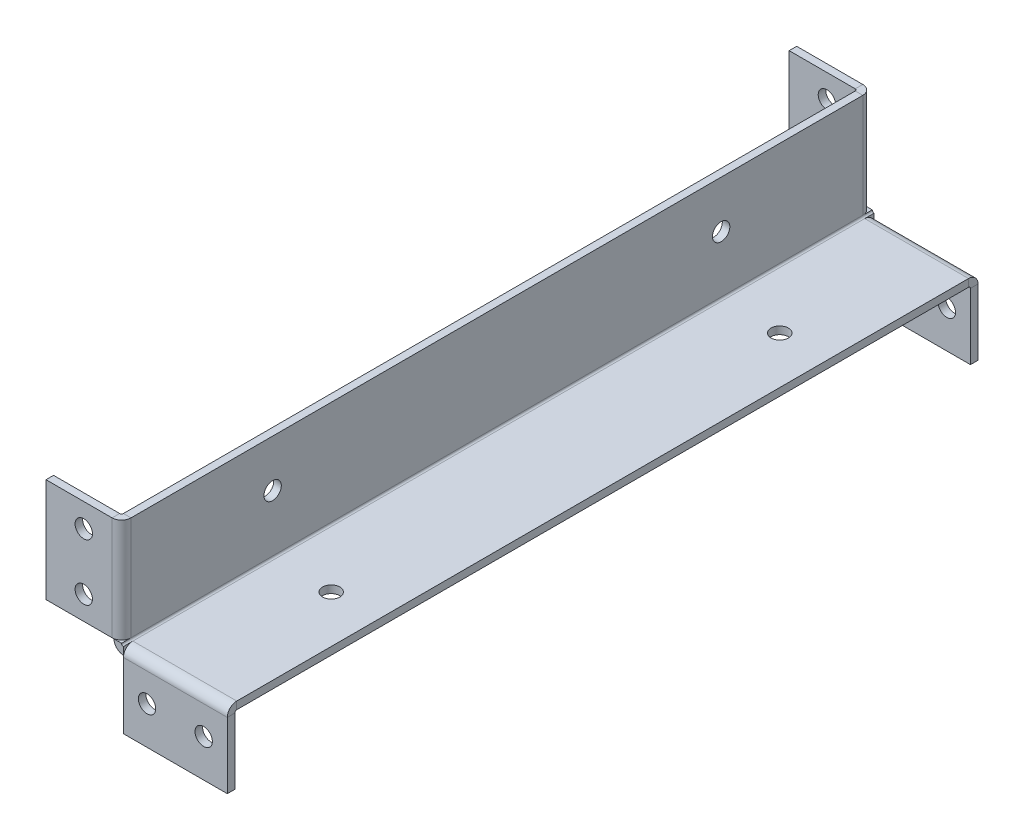
SolidWorks part; units mm, degrees
note: The reader was unsure of these and kept them because the rebuilt part matched: flange length of "Edge-Flange1", "Edge-Flange2".
ref_plane "Front Plane" through (0, 0, 0) normal (0, 0, 1) x (1, 0, 0)
ref_plane "Top Plane" through (0, 0, 0) normal (0, 1, 0) x (1, 0, 0)
ref_plane "Right Plane" through (0, 0, 0) normal (1, 0, 0) x (0, 0, -1)
sketch "Sketch1" plane through (0, 0, 0) normal (0, 1, 0) x (1, 0, 0)
  line L1 (30, 198.75) -> (-30, 198.75)
  line L2 (30, 198.75) -> (30, -198.75)
  line L3 (30, -198.75) -> (-30, -198.75)
  line L4 (-30, 198.75) -> (-30, -198.75)
  line L5 (30, 198.75) -> (-30, -198.75) construction
  line L6 (30, -198.75) -> (-30, 198.75) construction
  point P0 (0, 0)
  dimension "D1" = 60
  dimension "D2" = 397.5
sheet metal parameters "Sheet-Metal1" thickness 4 parameters "D1"=1
base flange "Base-Flange1" sketch "Sketch1" thickness 4 reverse thickness direction yes parameters "D1"=1
edge flange "Edge-Flange1" sketch "Sketch5" flange angle 90 flange length 60 flange position material inside bend radius 1 thickness 4 parameters "D6"=10
sketch "Sketch5" plane through (-30, 4, 0) normal (-1, 0, 0) x (0, 0, 1)
  line L2 (-198.75, 0) -> (-198.75, 56)
  line L3 (-198.75, 56) -> (198.75, 56)
  line L4 (198.75, 56) -> (198.75, 0)
  line L5 (-198.75, 0) -> (198.75, 0) construction
  line L6 (-198.75, 0) -> (198.75, 0)
bend "EdgeBend1" bend radius 1 bend angle 90 parameters "D5"=1
edge flange "Edge-Flange2" sketch "Sketch14" flange profiles "Sketch14", "Sketch15", "Sketch16", "Sketch17" flange angle 90 flange length 40 flange position material inside bend radius 1 thickness 4 relief none parameters "D6"=10, "D8"=0.5
sketch "Sketch14" plane through (-30, 0, 198.75) normal (0, 0, -1) x (0, -1, 0)
  line L1 (-5, 0) -> (-60, 0) construction
  line L2 (-60, 0) -> (-60, 36)
  line L3 (-60, 36) -> (-5, 36)
  line L4 (-5, 36) -> (-5, 0)
  line L5 (-5, 0) -> (-60, 0)
sketch "Sketch15" plane through (0, 0, 198.75) normal (0, 0, -1) x (1, 0, 0)
  line L0 (30, 0) -> (-25, 0) construction
  line L1 (30, 0) -> (-25, 0)
  line L2 (30, 0) -> (30, 36)
  line L3 (30, 36) -> (-25, 36)
  line L4 (-25, 36) -> (-25, 0)
sketch "Sketch16" plane through (-30, 0, -198.75) normal (0, 0, 1) x (0, 1, 0)
  line L0 (60, 0) -> (5, 0) construction
  line L1 (60, 0) -> (5, 0)
  line L2 (60, 0) -> (60, 36)
  line L3 (60, 36) -> (5, 36)
  line L4 (5, 36) -> (5, 0)
sketch "Sketch17" plane through (0, 0, -198.75) normal (0, 0, 1) x (-1, 0, 0)
  line L0 (25, 0) -> (-30, 0) construction
  line L1 (25, 0) -> (-30, 0)
  line L2 (25, 0) -> (25, 36)
  line L3 (25, 36) -> (-30, 36)
  line L4 (-30, 36) -> (-30, 0)
bend "EdgeBend2" bend radius 1 bend angle 90 parameters "D5"=2
bend "EdgeBend3" bend radius 1 bend angle 90 parameters "D5"=3
bend "EdgeBend4" bend radius 1 bend angle 90 parameters "D5"=4
bend "EdgeBend5" bend radius 1 bend angle 90 parameters "D5"=5
sketch "Sketch18" plane through (0, 0, 198.75) normal (0, 0, 1) x (1, 0, 0)
  line L0 (-25, 4) -> (30, 4) construction
  line L1 (-26, 60) -> (-26, 5) construction
  line L2 (-66, 60) -> (-31, 60) construction
  line L3 (30, -1) -> (30, -36) construction
  circle A0 centre (-46, 47.5) radius 4.6
  circle A1 centre (-46, 17.5) radius 4.6
  circle A2 centre (-12.5, -16) radius 4.6
  circle A3 centre (17.5, -16) radius 4.6
  dimension "D7" = 9.2
  dimension "D1" = 30
  dimension "D2" = 30
  dimension "D3" = 20
  dimension "D4" = 20
  dimension "D5" = 12.5
  dimension "D6" = 12.5
extrude "Extrude1" cut sketch "Sketch18" against normal through all normal cut yes
sketch "Sketch19" plane through (-26, 0, 0) normal (1, 0, 0) x (0, 0, -1)
  line L0 (-193.75, 60) -> (193.75, 60) construction
  line L1 (-198.75, 5) -> (-198.75, 60) construction
  line L2 (198.75, 5) -> (198.75, 60) construction
  circle A0 centre (-118.75, 35) radius 4.6
  circle A1 centre (118.75, 35) radius 4.6
  dimension "D4" = 9.2
  dimension "D1" = 25
  dimension "D2" = 80
  dimension "D3" = 80
extrude "Extrude2" cut sketch "Sketch19" against normal blind 4 normal cut yes
sketch "Sketch20" plane through (0, 4, 0) normal (0, 1, 0) x (1, 0, 0)
  line L0 (30, -193.75) -> (30, 193.75) construction
  line L1 (-25, -198.75) -> (30, -198.75) construction
  line L2 (30, 198.75) -> (-25, 198.75) construction
  circle A0 centre (5, 118.75) radius 4.6
  circle A1 centre (5, -118.75) radius 4.6
  dimension "D2" = 9.2
  dimension "D1" = 25
  dimension "D3" = 80
  dimension "D4" = 80
extrude "Extrude3" cut sketch "Sketch20" against normal blind 4 normal cut yes
flat pattern "Flat-Pattern1" [suppressed]
sketch "Bend-Lines1" plane through (0, 4, 0) normal (0, 1, 0) x (-1, 0, 0)
  line L0 (25, -126.4012) -> (-30, -126.4012) construction
  line L1 (82.8023, -126.4012) -> (27.8023, -126.4012) construction
  line L2 (-30, 126.4012) -> (25, 126.4012) construction
  line L3 (27.8023, 126.4012) -> (82.8023, 126.4012) construction
  line L4 (26.4012, -130) -> (26.4012, 130) construction
  line L5 (25, -126.4012) -> (-30, -126.4012) construction
  line L6 (82.8023, -126.4012) -> (27.8023, -126.4012) construction
  line L7 (-30, 126.4012) -> (25, 126.4012) construction
  line L8 (27.8023, 126.4012) -> (82.8023, 126.4012) construction
  line L9 (26.4012, -130) -> (26.4012, 130) construction
bend of the flat pattern "Flatten-<EdgeBend1>1"
bend of the flat pattern "Flatten-<EdgeBend2>1"
bend of the flat pattern "Flatten-<EdgeBend3>1"
bend of the flat pattern "Flatten-<EdgeBend4>1"
bend of the flat pattern "Flatten-<EdgeBend5>1"
